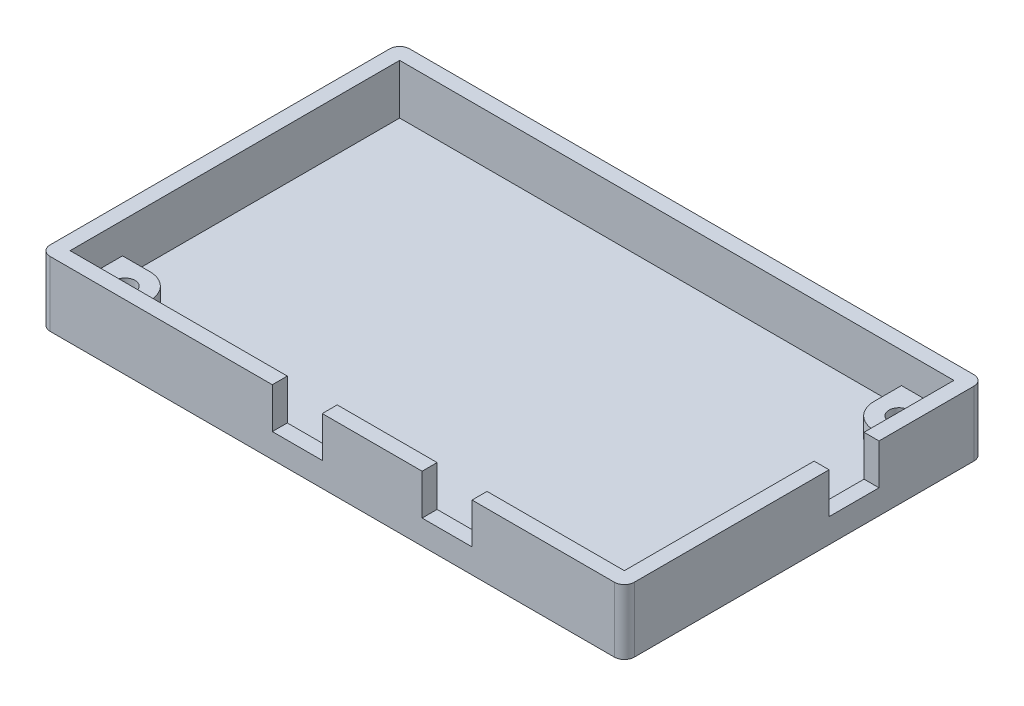
SolidWorks part; units mm, degrees
ref_plane "Front" through (0, 0, 0) normal (0, 0, 1) x (1, 0, 0)
ref_plane "Top" through (0, 0, 0) normal (0, 1, 0) x (1, 0, 0)
ref_plane "Right" through (0, 0, 0) normal (1, 0, 0) x (0, 0, -1)
sketch "Sketch1" plane through (0, 0, 0) normal (0, 1, 0) x (1, 0, 0)
  line L0 (-0.5, -0.5) -> (-0.5, 65.5)
  line L1 (0, 0) -> (110, 0)
  line L2 (0, 0) -> (0, 65)
  line L3 (0, 65) -> (110, 65)
  line L4 (110, 0) -> (110, 65)
  line L9 (-0.5, 65.5) -> (110.5, 65.5)
  line L10 (110.5, -0.5) -> (110.5, 65.5)
  line L11 (-0.5, -0.5) -> (110.5, -0.5)
  line L12 (-3.5, 68.5) -> (113.5, 68.5)
  line L13 (113.5, -3.5) -> (113.5, 68.5)
  line L14 (-3.5, -3.5) -> (113.5, -3.5)
  line L15 (-3.5, -3.5) -> (-3.5, 68.5)
  dimension "D1" = 110
  dimension "D2" = 65
  dimension "D3" = 0.5
  dimension "D4" = 3
extrude "Boss-Extrude1" add sketch "Sketch1" against normal blind 3 contours L0 L11 L10 L9 L4 L1 L2 L3 | L1 L4 L3 L2 | L15 L14 L13 L12 L11 L0 L9 L10 region at (-0.3709, 0, -32.5) region at (55, 0, -32.5) region at (55, 0, -67.1262)
extrude "Boss-Extrude2" add sketch "Sketch1<5>" along normal blind 10 contours L15 L14 L13 L12 L11 L0 L9 L10 region at (55, 0, -67.1262)
sketch "Sketch1<5>" plane through (0, 0, 0) normal (0, 1, 0) x (1, 0, 0) same geometry as "Sketch1"
sketch "Sketch2" plane through (0, 0, 0) normal (0, 1, 0) x (1, 0, 0)
  line L1 (110.5, 65.5) -> (100, 65.5)
  line L2 (110.5, 65.5) -> (110.5, 55)
  line L3 (110.5, 55) -> (105, 55)
  line L4 (100, 65.5) -> (100, 60)
  line L5 (-0.5, -0.5) -> (10, -0.5)
  line L6 (-0.5, -0.5) -> (-0.5, 10)
  line L7 (-0.5, 10) -> (5, 10)
  line L8 (10, -0.5) -> (10, 5)
  arc A0 (5, 10) -> (10, 5) centre (5, 5) cw
  arc A1 (105, 55) -> (100, 60) centre (105, 60) cw
  point P12 (10, 10)
  point P15 (100, 55)
  dimension "D5" = 5
  dimension "D1" = 10.5
  dimension "D2" = 10.5
  dimension "D3" = 10.5
  dimension "D4" = 10.5
extrude "Boss-Extrude3" add sketch "Sketch2" along normal blind 3.85
sketch "Sketch3" plane through (0, 3.85, 0) normal (0, 1, 0) x (1, 0, 0)
  line L0 (110.5, 55) -> (110.5, 65.5) construction
  line L1 (110.5, 65.5) -> (100, 65.5) construction
  line L2 (-0.5, 10) -> (-0.5, -0.5) construction
  line L3 (-0.5, -0.5) -> (10, -0.5) construction
  circle A0 centre (105, 60) radius 2
  circle A1 centre (5, 5) radius 2
  dimension "D3" = 4
  dimension "D4" = 4
  dimension "D1" = 5.5
  dimension "D2" = 5.5
  dimension "D5" = 5.5
  dimension "D6" = 5.5
extrude "Cut-Extrude1" cut sketch "Sketch3" against normal blind 4.78
fillet "Fillet1" radius 2 4 edges at (113.5, 3.5, 3.5) (-3.5, 3.5, 3.5) (-3.5, 3.5, -68.5) (113.5, 3.5, -68.5)
sketch "Sketch4" plane through (110.5, 0, 0) normal (-1, 0, 0) x (0, 0, 1)
  line L0 (0.5, 10) -> (-65.5, 10) construction
  line L1 (-47.5, 10) -> (-37.5, 10)
  line L2 (-47.5, 10) -> (-47.5, 1.87)
  line L3 (-47.5, 1.87) -> (-37.5, 1.87)
  line L4 (-37.5, 10) -> (-37.5, 1.87)
  line L5 (0.5, 0) -> (-55, 0) construction
  point P8 (-47.313, 9.8055)
  point P11 (-42.5, 10)
  dimension "D1" = 1.87
  dimension "D2" = 43
  dimension "D3" = 10
extrude "Cut-Extrude2" cut sketch "Sketch4" against normal through all contours L2 L3 L4 L1
sketch "Sketch5" plane through (0, 0, 0.5) normal (0, 0, -1) x (-1, 0, 0)
  line L0 (0.5, 10) -> (-110.5, 10) construction
  line L1 (-83, 10) -> (-73, 10)
  line L2 (-83, 10) -> (-83, 1.87)
  line L3 (-83, 1.87) -> (-73, 1.87)
  line L4 (-73, 10) -> (-73, 1.87)
  line L5 (-10, 0) -> (-110.5, 0) construction
  line L6 (-53, 10) -> (-43, 10)
  line L7 (-53, 10) -> (-53, 1.87)
  line L8 (-53, 1.87) -> (-43, 1.87)
  line L9 (-43, 10) -> (-43, 1.87)
  point P10 (-78, 10)
  point P11 (-48, 10)
  dimension "D1" = 1.87
  dimension "D2" = 1.87
  dimension "D3" = 32.5
  dimension "D4" = 62.5
  dimension "D5" = 10
  dimension "D6" = 10
extrude "Cut-Extrude3" cut sketch "Sketch5" against normal through all
